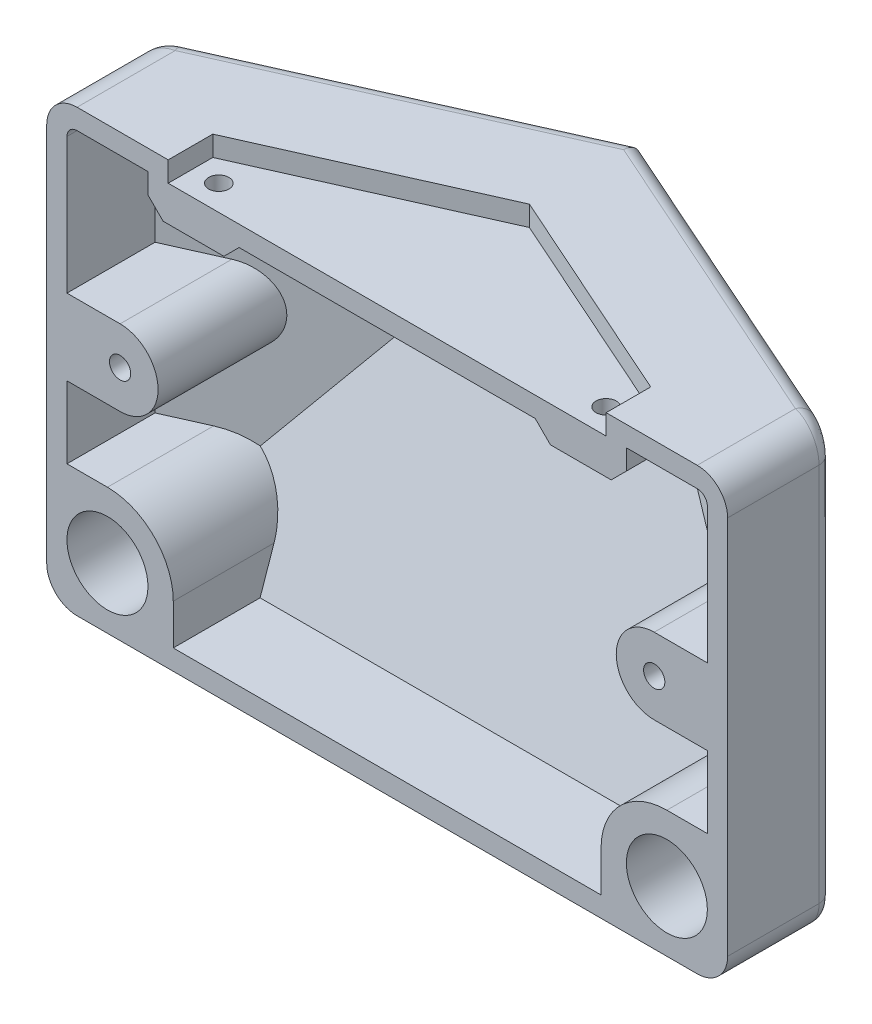
SolidWorks part; units mm, degrees
material "PLA"
ref_plane "Front Plane" through (0, 0, 0) normal (0, 0, 1) x (1, 0, 0)
ref_plane "Top Plane" through (0, 0, 0) normal (0, 1, 0) x (1, 0, 0)
ref_plane "Right Plane" through (0, 0, 0) normal (1, 0, 0) x (0, 0, -1)
sketch "Sketch1" plane through (0, 0, 0) normal (0, 0, 1) x (1, 0, 0)
  line L1 (-67.25, -43.5) -> (67.25, -43.5)
  line L2 (-67.25, -43.5) -> (-67.25, 43.5)
  line L3 (-67.25, 43.5) -> (67.25, 43.5)
  line L4 (67.25, -43.5) -> (67.25, 43.5)
  line L5 (-67.25, -43.5) -> (67.25, 43.5) construction
  line L6 (-67.25, 43.5) -> (67.25, -43.5) construction
  point P0 (0, 0)
  dimension "D1" = 134.5
  dimension "D2" = 87
extrude "Boss-Extrude1" add sketch "Sketch1" along normal blind 50
ref_point "Point2" parameters "D1"=20
ref_point "Point3" parameters "D1"=20
ref_plane "Plane1" through (0, 4.6227, 13.406) normal (0, -0.326, -0.9454) x (-1, 0, 0)
sketch "Sketch4" plane through (0, 4.6227, 13.406) normal (0, -0.326, -0.9454) x (-1, 0, 0)
  line L1 (-67.25, 41.1237) -> (67.25, 41.1237)
  line L2 (-67.25, 41.1237) -> (-67.25, -50.9034)
  line L3 (-67.25, -50.9034) -> (67.25, -50.9034)
  line L4 (67.25, 41.1237) -> (67.25, -50.9034)
extrude "Cut-Extrude1" cut sketch "Sketch4" along normal up to next
ref_point "Point4" parameters "D1"=20
ref_plane "Plane2" through (0, 0, 0) normal (-0.4074, 0, 0.9133) x (0.9133, 0, 0.4074)
sketch "Sketch5" plane through (0, 0, 0) normal (-0.4074, 0, 0.9133) x (0.9133, 0, 0.4074)
  line L1 (73.6381, 56.0732) -> (-31.4143, 56.0732)
  line L2 (73.6381, 56.0732) -> (73.6381, -43.5)
  line L3 (73.6381, -43.5) -> (-31.4143, -43.5)
  line L4 (-31.4143, 56.0732) -> (-31.4143, -43.5)
extrude "Cut-Extrude2" cut sketch "Sketch5" against normal up to next
mirror "Mirror1" about plane through (0, 0, 0) normal (1, 0, 0) of "Cut-Extrude2"
fillet "Fillet4" radius 6 4 edges at (-67.25, -43.5, 40) (-67.25, 43.5, 40) (67.25, -43.5, 40) (67.25, 43.5, 40)
shell "Shell1" thickness 4 removed face at (0, 0, 50)
sketch "Sketch2" plane through (0, 0, 50) normal (0, 0, 1) x (1, 0, 0)
  line L0 (-55.25, -18.5) -> (-63.25, -18.5)
  line L3 (61.25, -39.5) -> (42.25, -39.5)
  line L4 (-63.25, 37.5) -> (-63.25, -37.5) construction
  line L5 (-42.25, -31.5) -> (-42.25, -39.5)
  line L6 (-61.25, -39.5) -> (61.25, -39.5) construction
  line L7 (-63.25, -18.5) -> (-63.25, -37.5)
  line L8 (-61.25, -39.5) -> (-42.25, -39.5)
  line L9 (0, 0) -> (0, -50000) construction
  line L10 (63.25, -18.5) -> (63.25, -37.5)
  line L11 (42.25, -31.5) -> (42.25, -39.5)
  line L12 (55.25, -18.5) -> (63.25, -18.5)
  circle A0 centre (-55.25, -31.5) radius 8 construction
  arc A2 (-42.25, -31.5) -> (-55.25, -18.5) centre (-55.25, -31.5) ccw
  circle A3 centre (-55.25, -31.5) radius 13 construction
  arc A4 (-63.25, -37.5) -> (-61.25, -39.5) centre (-61.25, -37.5) ccw construction
  arc A5 (-63.25, -37.5) -> (-61.25, -39.5) centre (-61.25, -37.5) ccw
  circle A6 centre (55.25, -31.5) radius 8 construction
  arc A7 (63.25, -37.5) -> (61.25, -39.5) centre (61.25, -37.5) cw
  arc A8 (42.25, -31.5) -> (55.25, -18.5) centre (55.25, -31.5) cw
  line M8 (-63.25, -37.5) -> (-63.25, 37.5)
  line M12 (63.25, 37.5) -> (63.25, -37.5)
  arc M13 (63.25, -37.5) -> (61.25, -39.5) centre (61.25, -37.5) cw
  line M14 (61.25, -39.5) -> (-61.25, -39.5)
  arc M15 (-61.25, -39.5) -> (-63.25, -37.5) centre (-61.25, -37.5) cw
  dimension "D1" = 16
  dimension "D4" = 5
extrude "Boss-Extrude2" add sketch "Sketch2" against normal up to next contours L5 A2 L0 M8 M15 M14 | A8 L11 L12 M14 M13 M12 region at (-53.4108, -29.6608, 50) region at (53.4108, -29.6608, 50)
sketch "Sketch6" plane through (0, 0, 50) normal (0, 0, 1) x (1, 0, 0)
  circle A0 centre (-55.25, -31.5) radius 8
  circle A1 centre (55.25, -31.5) radius 8
  dimension "D1" = 16
extrude "Cut-Extrude3" cut sketch "Sketch6" against normal blind 15
sketch "Sketch3" plane through (0, 0, 50) normal (0, 0, -1) x (-1, 0, 0)
  line L0 (52.75, 10.7) -> (63.25, 10.7)
  line L1 (0, 0) -> (0, -50000) construction
  line L2 (63.25, 37.5) -> (63.25, -18.5) construction
  line L3 (63.25, 10.7) -> (63.25, -4.3)
  line L4 (63.25, -4.3) -> (52.75, -4.3)
  line L5 (-63.25, -4.3) -> (-52.75, -4.3)
  line L6 (-63.25, 10.7) -> (-63.25, -4.3)
  line L7 (-52.75, 10.7) -> (-63.25, 10.7)
  circle A0 centre (52.75, 3.2) radius 2.1 construction
  arc A1 (55.25, -18.5) -> (42.25, -31.5) centre (55.25, -31.5) ccw construction
  arc A4 (52.75, 10.7) -> (52.75, -4.3) centre (52.75, 3.2) ccw
  circle A5 centre (-52.75, 3.2) radius 2.1 construction
  arc A6 (-52.75, 10.7) -> (-52.75, -4.3) centre (-52.75, 3.2) cw
  dimension "D1" = 34.7
  dimension "D2" = 2.5
  dimension "D3" = 4.2
  dimension "D4" = 15
extrude "Boss-Extrude3" add sketch "Sketch3" along normal up to next
sketch "Sketch8" plane through (0, 0, 50) normal (0, 0, 1) x (1, 0, 0)
  circle A0 centre (-52.75, 3.2) radius 2.1
  circle A1 centre (52.75, 3.2) radius 2.1
  dimension "D1" = 4.2
extrude "Cut-Extrude4" cut sketch "Sketch8" against normal up to surface (23.0252 mm away) contours A0 up to face at (-51.9446, 7.2957, 27.5523)
extrude "Cut-Extrude8" cut sketch "Sketch8<3>" against normal up to surface (21.1516 mm away) contours A1 up to face at (51.9446, 7.2957, 27.5523)
sketch "Sketch8<3>" plane through (0, 0, 50) normal (0, 0, 1) x (1, 0, 0) same geometry as "Sketch8"
sketch "Sketch10" plane through (0, 39.5, 0) normal (0, -1, 0) x (1, 0, 0)
  line L0 (0, 0) -> (0, 50000) construction
  line L1 (61.25, 50) -> (-61.25, 50) construction
  line L2 (-43.25, 50) -> (43.25, 50) construction
  line L3 (-43.25, 50) -> (-43.25, 41.1935) construction
  line L5 (43.25, 50) -> (43.25, 41.1935) construction
  line L6 (47.25, 50) -> (47.25, 38.5979)
  line L7 (47.25, 38.5979) -> (0, 17.5198)
  line L10 (0, 17.5198) -> (-47.25, 38.5979)
  line L18 (0, 21.8998) -> (-53.102, 45.5884)
  line L19 (53.102, 45.5884) -> (0, 21.8998)
  line L20 (0, 21.8998) -> (-43.25, 41.1935) construction
  line L21 (43.25, 41.1935) -> (0, 21.8998) construction
  line L25 (-47.25, 50) -> (-47.25, 38.5979)
  line L26 (-47.25, 50) -> (47.25, 50)
  dimension "D1" = 43.25
  dimension "D2" = 43.25
  dimension "D3" = 20
  dimension "D4" = 4
extrude "Boss-Extrude4" add sketch "Sketch10" along normal blind 4
sketch "Sketch11" plane through (0, 43.5, 0) normal (0, 1, 0) x (1, 0, 0)
  line L5 (-47.25, -50) -> (47.25, -50)
  line L7 (-47.25, -50) -> (47.25, -50) construction
  line L9 (-47.25, -38.5979) -> (-47.25, -50)
  line L21 (-47.25, -38.5979) -> (-47.25, -50) construction
  line L23 (0, -17.5198) -> (-47.25, -38.5979)
  line L25 (43.25, -50) -> (43.25, -41.1935)
  line L26 (43.25, -41.1935) -> (0, -21.8998)
  line L27 (0, -21.8998) -> (-43.25, -41.1935)
  line L28 (-43.25, -41.1935) -> (-43.25, -50)
  line L29 (-43.25, -50) -> (43.25, -50)
  line L30 (0, -17.5198) -> (-47.25, -38.5979) construction
  line L31 (47.25, -38.5979) -> (0, -17.5198)
  line L32 (47.25, -38.5979) -> (0, -17.5198) construction
  line L33 (47.25, -50) -> (47.25, -38.5979)
  line L34 (47.25, -50) -> (47.25, -38.5979) construction
  dimension "D1" = 0
  dimension "D2" = 4
extrude "Cut-Extrude5" cut sketch "Sketch11" against normal blind 4
sketch "Sketch12" plane through (0, 35.5, 0) normal (0, -1, 0) x (1, 0, 0)
  line L1 (-43.25, 41.1935) -> (-43.25, 50) construction
  line L2 (-38.25, 48.2332) -> (-41.05, 46.6166) construction
  line L3 (-41.05, 46.6166) -> (-41.05, 43.3834) construction
  line L4 (-41.05, 43.3834) -> (-38.25, 41.7668) construction
  line L5 (-38.25, 41.7668) -> (-35.45, 43.3834) construction
  line L6 (-35.45, 43.3834) -> (-35.45, 46.6166) construction
  line L7 (-35.45, 46.6166) -> (-38.25, 48.2332) construction
  line L8 (-43.25, 50) -> (43.25, 50) construction
  line L9 (-38.25, 45) -> (-38.25, 48.2332) construction
  line L10 (0, 0) -> (0, -50000) construction
  line L11 (-44.25, 40) -> (-32.25, 40)
  line L12 (-44.25, 40) -> (-44.25, 50)
  line L13 (-44.25, 50) -> (-32.25, 50)
  line L14 (-32.25, 40) -> (-32.25, 50)
  line L15 (-44.25, 40) -> (-32.25, 50) construction
  line L16 (-44.25, 50) -> (-32.25, 40) construction
  line L17 (44.25, 50) -> (32.25, 40) construction
  line L18 (44.25, 40) -> (32.25, 50) construction
  line L19 (38.25, 45) -> (38.25, 48.2332) construction
  line L20 (35.45, 46.6166) -> (38.25, 48.2332) construction
  line L21 (35.45, 43.3834) -> (35.45, 46.6166) construction
  line L22 (38.25, 41.7668) -> (35.45, 43.3834) construction
  line L23 (41.05, 43.3834) -> (38.25, 41.7668) construction
  line L24 (41.05, 46.6166) -> (41.05, 43.3834) construction
  line L25 (38.25, 48.2332) -> (41.05, 46.6166) construction
  line L26 (32.25, 40) -> (32.25, 50)
  line L27 (44.25, 50) -> (32.25, 50)
  line L28 (44.25, 40) -> (44.25, 50)
  line L29 (44.25, 40) -> (32.25, 40)
  circle A0 centre (-38.25, 45) radius 2.8 construction
  circle A1 centre (38.25, 45) radius 2.8 construction
  dimension "D1" = 5.6
  dimension "D2" = 5
  dimension "D3" = 5
  dimension "D4" = 3
extrude "Boss-Extrude5" add sketch "Sketch12" along normal blind 3
sketch "Sketch15" plane through (0, 32.5, 0) normal (0, -1, 0) x (-1, 0, 0)
  line L0 (44.25, -50) -> (32.25, -40) construction
  line L1 (0, 0) -> (0, -50000) construction
  circle A0 centre (38.25, -45) radius 2
  circle A1 centre (-38.25, -45) radius 2
  dimension "D1" = 4
extrude "Cut-Extrude7" cut sketch "Sketch15" against normal up to next
sketch "Sketch13" plane through (0, 32.5, 0) normal (0, -1, 0) x (1, 0, 0)
  line L0 (-32.25, 50) -> (-44.25, 40) construction
  line L2 (-44.25, 40) -> (-32.25, 40) construction
  line L3 (-44.25, 50) -> (-44.25, 40) construction
  line L4 (-38.25, 45) -> (-38.25, 48.2332) construction
  line L5 (-38.25, 48.2332) -> (-41.05, 46.6166)
  line L6 (-41.05, 46.6166) -> (-41.05, 43.3834)
  line L7 (-41.05, 43.3834) -> (-38.25, 41.7668)
  line L8 (-38.25, 41.7668) -> (-35.45, 43.3834)
  line L9 (-35.45, 43.3834) -> (-35.45, 46.6166)
  line L10 (-35.45, 46.6166) -> (-38.25, 48.2332)
  line L11 (0, 0) -> (0, 50000) construction
  line L12 (38.25, 45) -> (38.25, 48.2332) construction
  line L13 (32.25, 50) -> (44.25, 40) construction
  line L14 (35.45, 46.6166) -> (38.25, 48.2332)
  line L15 (35.45, 43.3834) -> (35.45, 46.6166)
  line L16 (38.25, 41.7668) -> (35.45, 43.3834)
  line L17 (41.05, 43.3834) -> (38.25, 41.7668)
  line L18 (41.05, 46.6166) -> (41.05, 43.3834)
  line L19 (38.25, 48.2332) -> (41.05, 46.6166)
  circle A0 centre (-38.25, 45) radius 2.8 construction
  circle A1 centre (38.25, 45) radius 2.8 construction
  dimension "D1" = 5.6
extrude "Cut-Extrude6" cut sketch "Sketch13" against normal blind 2.7
fillet "Fillet5" radius 3 11 edges at (66.8524, -39.6477, 29.8226) (30.625, 43.5, 13.6617) (65.4926, 41.7426, 29.216) (63.6928, -42.9802, 29.8208) (-63.6928, -42.9802, 29.8208) (-66.8524, -39.6477, 29.8226) (-67.25, 0, 30) (-65.4926, 41.7426, 29.216) (67.25, 0, 30) (0, -43.5, 30) (-30.625, 43.5, 13.6617)
chamfer "Chamfer1" distance 3 angle 45 4 edges at (-44.25, 35.5, 45) (32.25, 35.5, 45) (44.25, 35.5, 45) (-32.25, 35.5, 45)
